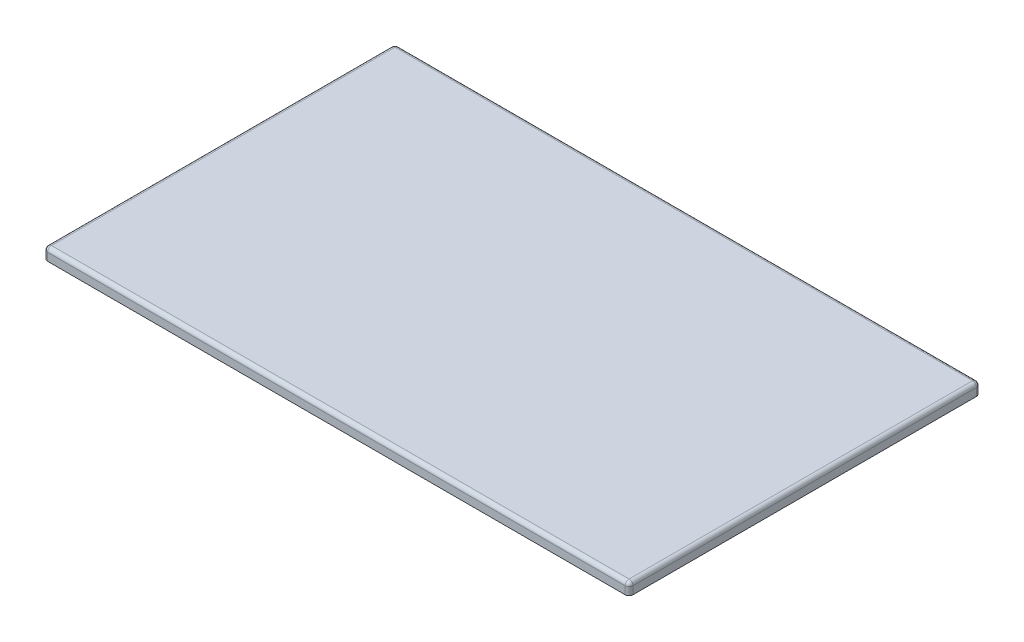
SolidWorks part; units mm, degrees
ref_plane "Plan de face" through (0, 0, 0) normal (0, 0, 1) x (1, 0, 0)
ref_plane "Plan de dessus" through (0, 0, 0) normal (0, 1, 0) x (1, 0, 0)
ref_plane "Plan de droite" through (0, 0, 0) normal (1, 0, 0) x (0, 0, -1)
sketch "Esquisse1" plane through (0, 0, 0) normal (0, 1, 0) x (1, 0, 0)
  line L1 (0, 0) -> (1500, 0)
  line L2 (0, 0) -> (0, 900)
  line L3 (0, 900) -> (1500, 900)
  line L4 (1500, 0) -> (1500, 900)
  dimension "D1" = 900
  dimension "D2" = 1500
extrude "Boss.-Extru.1" add sketch "Esquisse1" along normal blind 30
fillet "Congé1" radius 10 4 edges at (750, 30, -900) (1500, 30, -450) (750, 30, 0) (0, 30, -450)
fillet "Congé2" radius 10 8 edges at (1497.0711, 27.0711, -897.0711) (2.9289, 27.0711, -897.0711) (2.9289, 27.0711, -2.9289) (1497.0711, 27.0711, -2.9289) (1500, 10, -900) (0, 10, -900) (0, 10, 0) (1500, 10, 0)
sketch "Esquisse2" plane through (0, 0, 0) normal (0, -1, 0) x (1, 0, 0)
  line L0 (100, -100) -> (150, -100) construction
  line L1 (100, -90) -> (150, -90)
  line L2 (100, -110) -> (150, -110)
  line L3 (0, -890) -> (0, -10) construction
  line L4 (10, 0) -> (1490, 0) construction
  line L5 (750, 0) -> (750, -900) construction
  line L6 (1490, -900) -> (10, -900) construction
  line L7 (0, -450) -> (1500, -450) construction
  line L8 (1500, -10) -> (1500, -890) construction
  line L9 (1400, -100) -> (1350, -100) construction
  line L10 (1400, -90) -> (1350, -90)
  line L11 (1400, -110) -> (1350, -110)
  line L12 (1400, -800) -> (1350, -800) construction
  line L13 (1400, -810) -> (1350, -810)
  line L14 (1400, -790) -> (1350, -790)
  line L15 (100, -800) -> (150, -800) construction
  line L16 (100, -810) -> (150, -810)
  line L17 (100, -790) -> (150, -790)
  arc A0 (100, -90) -> (100, -110) centre (100, -100) ccw
  arc A1 (150, -110) -> (150, -90) centre (150, -100) ccw
  arc A2 (1400, -90) -> (1400, -110) centre (1400, -100) cw
  arc A3 (1350, -110) -> (1350, -90) centre (1350, -100) cw
  arc A4 (1400, -810) -> (1400, -790) centre (1400, -800) ccw
  arc A5 (1350, -790) -> (1350, -810) centre (1350, -800) ccw
  arc A6 (100, -810) -> (100, -790) centre (100, -800) cw
  arc A7 (150, -790) -> (150, -810) centre (150, -800) cw
  point P2 (125, -100)
  point P21 (1375, -100)
  point P28 (1375, -800)
  point P35 (125, -800)
  dimension "D2" = 10
  dimension "D1" = 50
  dimension "D3" = 100
  dimension "D4" = 100
extrude "Enlèv. mat.-Extru.1" cut sketch "Esquisse2" against normal blind 15
